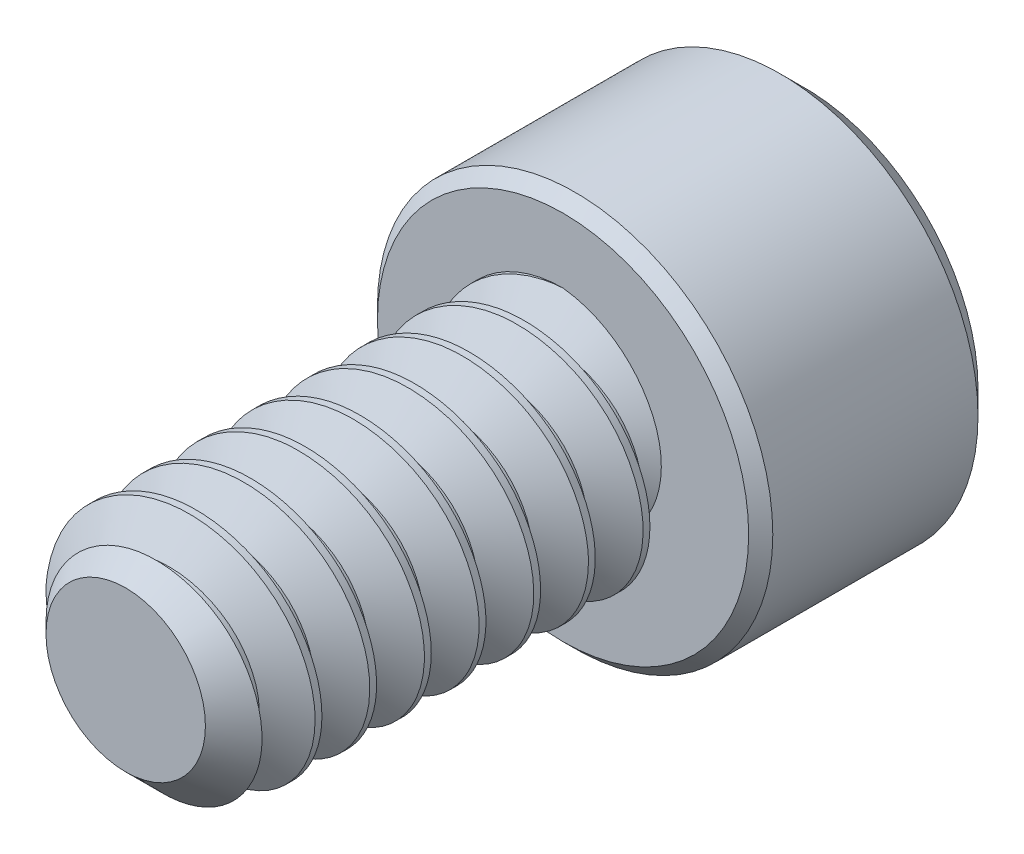
SolidWorks part; units mm, degrees
ref_plane "Front Plane" through (0, 0, 0) normal (0, 0, 1) x (1, 0, 0)
ref_plane "Top Plane" through (0, 0, 0) normal (0, 1, 0) x (1, 0, 0)
ref_plane "Right Plane" through (0, 0, 0) normal (1, 0, 0) x (0, 0, -1)
sketch "Sketch1" plane through (0, 0, 0) normal (0, 0, 1) x (1, 0, 0)
  line L0 (0, 1.7526) -> (0, -1.7526) construction
  circle A0 centre (0, 0) radius 1.7526
  dimension "OD" = 3.5052
extrude "Extrude1" add sketch "Sketch1" against normal blind 6.35
sketch "Sketch2" plane through (0, 0, 0) normal (0, 0, 1) x (1, 0, 0)
  circle A0 centre (0, 0) radius 1.7526 construction
  circle A1 centre (0, 0) radius 1.7526
curve "Helix/Spiral1" pitch 0.7937 height 7.1437 turns 9 parameters "pitch"=0.7937
chamfer "Chamfer3" distance 0.5953 angle 45 1 edges at (1.7526, 0, 0)
sketch "Sketch3" plane through (0, 0, 0) normal (1, 0, 0) x (0, 0, -1)
  line L0 (-0.6945, 1.7526) -> (-0.3969, 1.237)
  line L1 (-0.3969, 1.237) -> (-0.2977, 1.237)
  line L2 (-0.2977, 1.237) -> (0, 1.7526)
  line L3 (-0.6945, 1.7526) -> (0, 1.7526)
  line L4 (-0.3473, 1.7526) -> (-0.3473, 1.237) construction
  line L5 (-0.5457, 1.4948) -> (-0.1488, 1.4948) construction
  line L6 (0, 1.7526) -> (0, -1.7526) construction
  dimension "D1" = 0.0992
  dimension "D2" = 0.3969
  dimension "D3" = 60
sweep "Cut-Sweep1" cut profiles "Sketch3" path "Helix/Spiral1"
sketch "Sketch6" plane through (0, 0, -6.35) normal (0, 0, -1) x (-1, 0, 0)
  circle A0 centre (0, 0) radius 2.8702
  dimension "head dia" = 5.7404
extrude "Extrude2" add sketch "Sketch6" along normal blind 3.5052
sketch "Sketch7" plane through (0, 0, -9.8552) normal (0, 0, -1) x (-1, 0, 0)
  line L1 (0, 1.604) -> (-1.3891, 0.802)
  line L2 (-1.3891, 0.802) -> (-1.3891, -0.802)
  line L3 (-1.3891, -0.802) -> (0, -1.604)
  line L4 (0, -1.604) -> (1.3891, -0.802)
  line L5 (1.3891, -0.802) -> (1.3891, 0.802)
  line L6 (1.3891, 0.802) -> (0, 1.604)
  circle A0 centre (0, 0) radius 1.3891 construction
  dimension "hex dia" = 2.7781
extrude "Cut-Extrude1" cut sketch "Sketch7" against normal blind 2.0836
sketch "Sketch8" plane through (0, 0, -9.8552) normal (0, 0, -1) x (-1, 0, 0)
  circle A0 centre (0, 0) radius 1.604
extrude "Cut-Extrude2" cut sketch "Sketch8" against normal blind 0.3505 draft 45
chamfer "Chamfer1" distance 0.3505 angle 45 1 edges at (-2.8702, 0, -9.8552)
chamfer "Chamfer2" distance 0.1753 angle 45 1 edges at (-2.8702, 0, -6.35)
sketch "Sketch9" plane through (0, 0, 0) normal (1, 0, 0) x (0, 0, -1)
  line L0 (0, 1.7526) -> (0, -1.7526) construction
  line L1 (4.3656, 1.7526) -> (4.3656, -1.7526) construction
  line L2 (6.35, 2.8702) -> (6.35, -2.8702) construction
  line L3 (9.8552, 2.8702) -> (9.8552, -2.8702) construction
  line L4 (9.8552, 0) -> (0, 0) construction
  dimension "D1" = 4.3656
  dimension "D2" = 3.5052
  dimension "D3" = 5.7404
  dimension "D4" = 6.35
equation "\"D3@Helix/Spiral1\" = \"screw length@Extrude1\"+\"pitch@Helix/Spiral1\""
equation "\"D1@Sketch3\" = \"pitch@Helix/Spiral1\"*.125"
equation "\"D2@Sketch3\" = \"pitch@Helix/Spiral1\"*.5"
equation "\"D1@Cut-Extrude1\" = \"hex dia@Sketch7\"*.75"
equation "\"D1@Chamfer1\" = \"head depth@Extrude2\"/10"
equation "\"D1@Sketch9\" = \"pitch@Helix/Spiral1\"*5.5"
equation "\"D1@Chamfer2\" = \"D1@Chamfer1\"/2"
equation "\"D1@Cut-Extrude2\" = \"D1@Chamfer2\"*2"
equation "\"D1@Chamfer3\" = \"pitch@Helix/Spiral1\"*.750"
equation "\"D2@Sketch9\" = \"head depth@Extrude2\""
equation "\"D3@Sketch9\" = \"head dia@Sketch6\""
equation "\"D4@Sketch9\" = \"screw length@Extrude1\""
